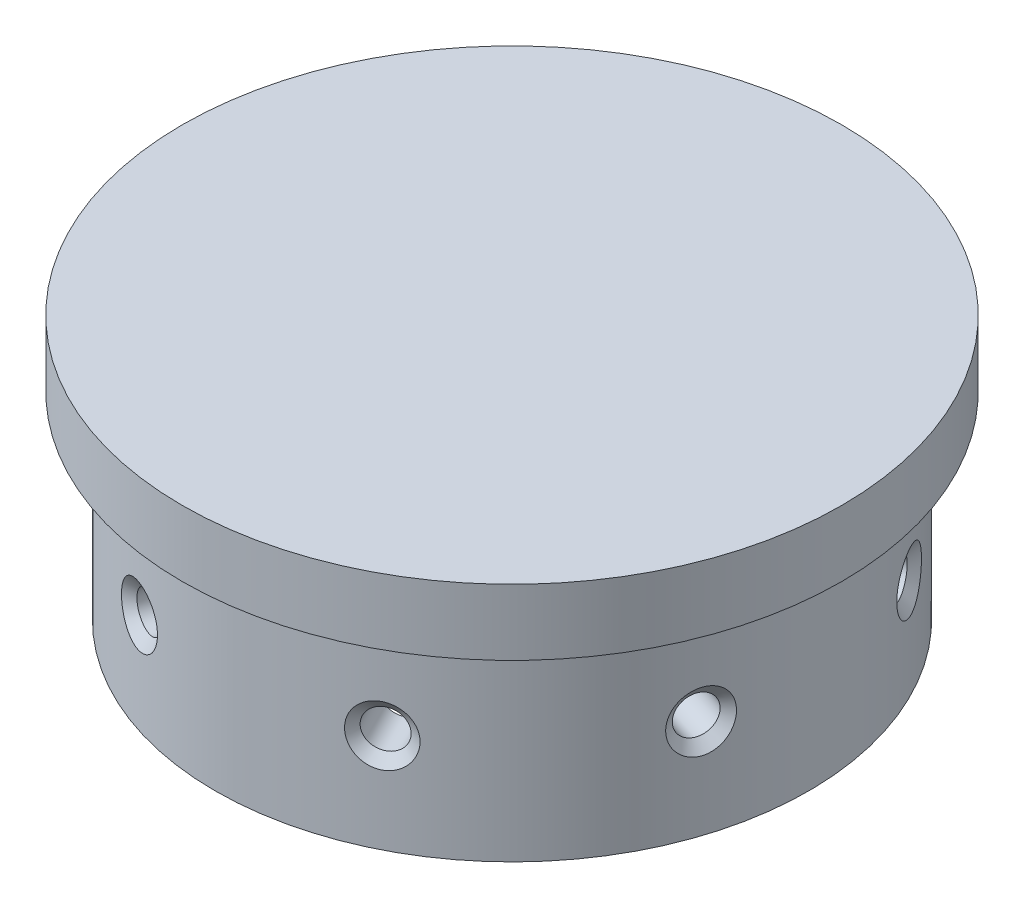
SolidWorks part; units mm, degrees
ref_plane "Front Plane" through (0, 0, 0) normal (0, 0, 1) x (1, 0, 0)
ref_plane "Top Plane" through (0, 0, 0) normal (0, 1, 0) x (1, 0, 0)
ref_plane "Right Plane" through (0, 0, 0) normal (1, 0, 0) x (0, 0, -1)
sketch "Sketch1" plane through (0, 0, 0) normal (0, 1, 0) x (1, 0, 0)
  circle A0 centre (0, 0) radius 28.575
  circle A1 centre (0, 0) radius 23.495
  dimension "D1" = 57.15
  dimension "D2" = 46.99
extrude "Boss-Extrude1" add sketch "Sketch1" along normal blind 19.05
hole_wizard "CSK for #4 Flat Head Machine Screw (100)1" positions "3DSketch1" profile "Sketch2" countersink size "#4" standard "ANSI Inch" end condition up to next
sketch3d "3DSketch1"
  point P0 (12.9332, 9.525, 25.4807)
  dimension "D1" = 9.525
sketch "Sketch2" plane through (12.9332, 9.525, 25.4807) normal (0, 1, 0) x (0.8917, 0, -0.4526)
  line L0 (0, 0) -> (0, 5.08)
  line L1 (0, 5.08) -> (1.8288, 5.08)
  line L2 (1.8288, 5.08) -> (1.8288, 0.8632)
  line L3 (1.8288, 0.8632) -> (2.8575, 0)
  line L5 (2.8575, 0) -> (0, 0)
  line L6 (-1.8288, 0.8632) -> (-2.8575, 0) construction
  line L11 (0, -6.35) -> (0, 107.95) construction
  dimension "Thru Hole Dia." = 3.6576
  dimension "Thru Hole Depth" = 5.08
  dimension "Near C'Sink Dia." = 5.715
  dimension "Near C'Sink Angle" = 100
pattern_circular "CirPattern1" count 8 over 360 about axis through (0, 19.05, 0) along (0, -1, 0) of "CSK for #4 Flat Head Machine Screw (100)1"
sketch "Sketch4" plane through (0, 19.05, 0) normal (0, 1, 0) x (1, 0, 0)
  circle A0 centre (0, 0) radius 31.75
  dimension "D1" = 63.5
extrude "Boss-Extrude2" add sketch "Sketch4" along normal blind 6.35
